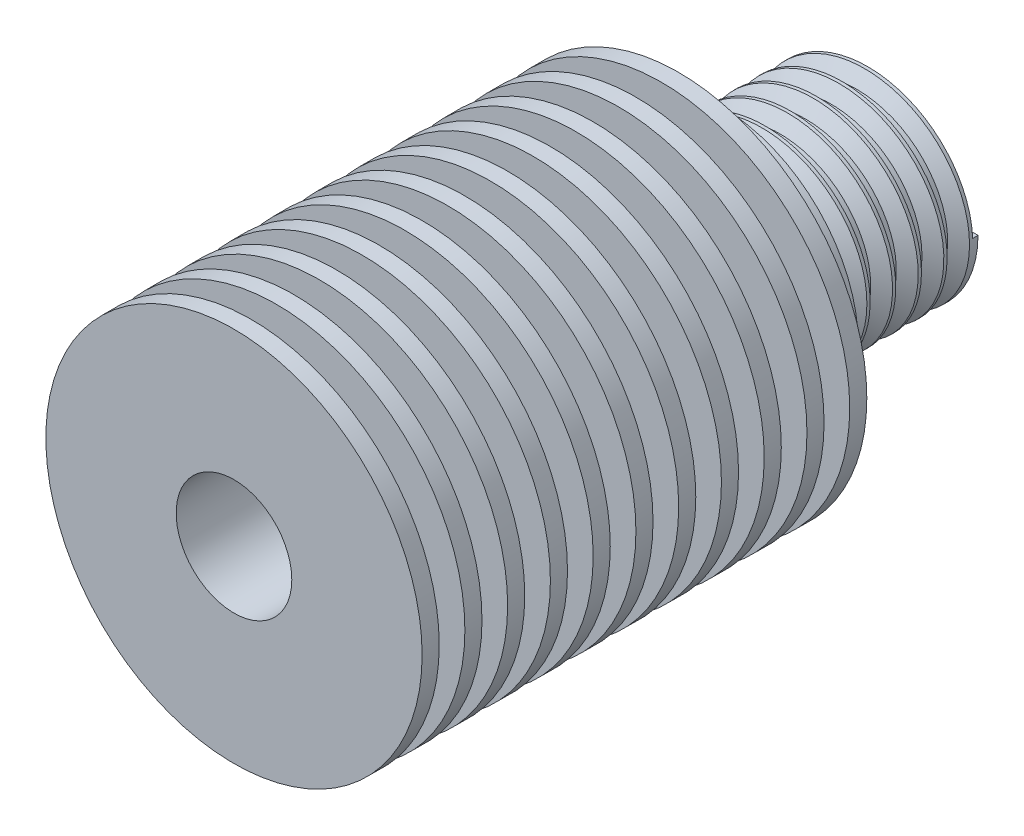
SolidWorks part; units mm, degrees
material "6061-T6 (SS)"
ref_plane "Front" through (0, 0, 0) normal (0, 0, 1) x (1, 0, 0)
ref_plane "Top" through (0, 0, 0) normal (0, 1, 0) x (1, 0, 0)
ref_plane "Right" through (0, 0, 0) normal (1, 0, 0) x (0, 0, -1)
sketch "Sketch1" plane through (0, 0, 0) normal (0, 1, 0) x (1, 0, 0)
  line L0 (0, 0) -> (0, 37.5) construction
  line L1 (3.3802, 0) -> (11, 0)
  line L2 (11, 0) -> (11, 1)
  line L3 (11, 1) -> (6.15, 1)
  line L4 (6.15, 1) -> (6.15, 2.5)
  line L5 (6.15, 2.5) -> (11, 2.5)
  line L6 (11, 2.5) -> (11, 3.5)
  line L7 (11, 3.5) -> (6.05, 3.5)
  line L8 (6.05, 3.5) -> (6.05, 5)
  line L9 (6.05, 5) -> (11, 5)
  line L10 (11, 5) -> (11, 6)
  line L11 (11, 6) -> (5.95, 6)
  line L12 (5.95, 6) -> (5.95, 7.5)
  line L13 (5.95, 7.5) -> (11, 7.5)
  line L14 (11, 7.5) -> (11, 8.5)
  line L15 (11, 8.5) -> (5.7, 8.5)
  line L16 (5.7, 8.5) -> (5.7, 10)
  line L17 (5.7, 10) -> (11, 10)
  line L18 (11, 10) -> (11, 11)
  line L19 (11, 11) -> (5.5, 11)
  line L20 (5.5, 11) -> (5.5, 12.5)
  line L21 (5.5, 12.5) -> (11, 12.5)
  line L22 (11, 12.5) -> (11, 13.5)
  line L23 (11, 13.5) -> (5.4, 13.5)
  line L24 (5.4, 13.5) -> (5.4, 15)
  line L25 (5.4, 15) -> (11, 15)
  line L26 (11, 15) -> (11, 16)
  line L27 (11, 16) -> (5.2, 16)
  line L28 (5.2, 16) -> (5.2, 17.5)
  line L29 (5.2, 17.5) -> (11, 17.5)
  line L30 (11, 17.5) -> (11, 18.5)
  line L31 (11, 18.5) -> (5, 18.5)
  line L32 (5, 18.5) -> (5, 20)
  line L33 (5, 20) -> (11, 20)
  line L34 (11, 20) -> (11, 21)
  line L35 (11, 21) -> (4.8, 21)
  line L36 (4.8, 21) -> (4.8, 22.5)
  line L37 (4.8, 22.5) -> (11, 22.5)
  line L38 (11, 22.5) -> (11, 23.5)
  line L39 (11, 23.5) -> (4.6, 23.5)
  line L40 (4.6, 23.5) -> (4.6, 25)
  line L41 (4.6, 25) -> (11, 25)
  line L42 (11, 25) -> (11, 26)
  line L43 (11, 26) -> (4.4, 26)
  line L44 (4.4, 26) -> (4.4, 27.5)
  line L45 (4.4, 27.5) -> (8, 27.5)
  line L46 (8, 27.5) -> (8, 28.5)
  line L47 (8, 28.5) -> (6, 28.5)
  line L48 (6, 28.5) -> (6, 37.5)
  line L49 (3.3802, 0) -> (3.3802, 15)
  line L50 (6, 37.5) -> (2.3173, 37.5)
  line L51 (2.3173, 37.5) -> (2.3173, 27.5)
  line L52 (2.3173, 27.5) -> (1.8875, 27.0115)
  line L53 (1.8875, 27.0115) -> (1.8875, 15)
  line L54 (1.8875, 15) -> (3.3802, 15)
  dimension "D1" = 37.5
  dimension "D2" = 1
  dimension "D3" = 1.5
  dimension "D4" = 4.85
  dimension "D5" = 4.95
  dimension "D6" = 5.05
  dimension "D7" = 5.3
  dimension "D8" = 5.5
  dimension "D9" = 5.6
  dimension "D10" = 5.8
  dimension "D11" = 6
  dimension "D12" = 6.2
  dimension "D13" = 6.4
  dimension "D14" = 6.6
  dimension "D15" = 16
  dimension "D16" = 22
  dimension "D17" = 1
  dimension "D18" = 12
  dimension "D19" = 15
  dimension "D20" = 10
revolve "Revolve1" add sketch "Sketch1" angle 360 about L0
thread "Thread1" pitch 1.5 method cut profile "Thread Profile1" start angle 0, offset 1, length 9, pitch 1.5, diameter 12
ref_plane "Plane1" through (6, 0, -38.5) normal (0, -1, 0) x (1, 0, 0)
sketch "Thread Profile1" plane through (6, 0, -38.5) normal (0, -1, 0) x (1, 0, 0)
  line L0 (0, 0) -> (0, 1.5) construction
  line L11 (0, 0) -> (0, 1.3125)
  line L12 (0, 1.3125) -> (-0.8119, 0.8437)
  line L13 (-0.8119, 0.8437) -> (-0.8119, 0.4687)
  line L15 (-0.8119, 0.4687) -> (0, 0)
  line L17 (-0.8119, 0.6562) -> (0, 0.6562) construction
  point P2 (0, 0)
  dimension "Pitch" = 1.5
  dimension "Profile_Angle" = 60
  dimension "Profile_Land" = 0.375
  dimension "Profile_Height" = 0.8119
